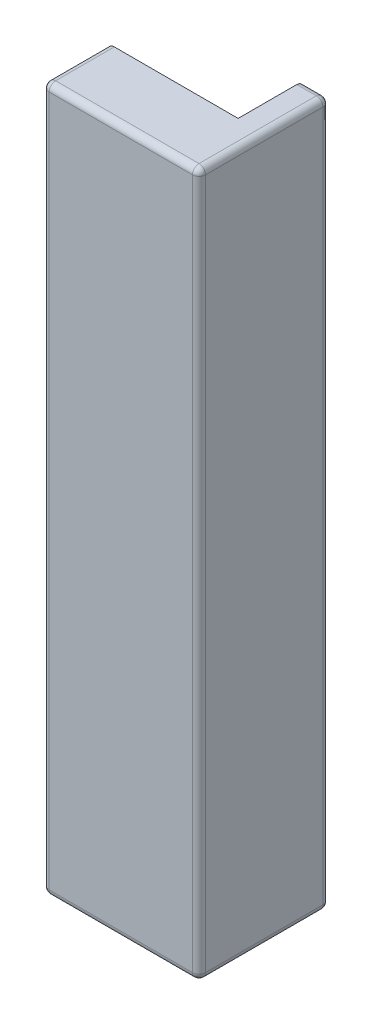
SolidWorks part; units mm, degrees
ref_plane "前基準面" through (0, 0, 0) normal (0, 0, 1) x (1, 0, 0)
ref_plane "上基準面" through (0, 0, 0) normal (0, 1, 0) x (1, 0, 0)
ref_plane "右基準面" through (0, 0, 0) normal (1, 0, 0) x (0, 0, -1)
sketch "草圖1" plane through (0, 0, 0) normal (0, 0, 1) x (1, 0, 0)
  line L1 (-30.8979, 20.8535) -> (-18.8979, 20.8535)
  line L2 (-30.8979, 20.8535) -> (-30.8979, -33.1465)
  line L3 (-30.8979, -33.1465) -> (-18.8979, -33.1465)
  line L4 (-18.8979, 20.8535) -> (-18.8979, -33.1465)
  dimension "D1" = 54
  dimension "D2" = 12
extrude "填料-伸長1" add sketch "草圖1" along normal blind 10 contours L2 L1 L4 L3
sketch "草圖2" plane through (-30.8979, 0, 0) normal (-1, 0, 0) x (0, 0, 1)
  line L0 (0, 20.8535) -> (0, -33.1465) construction
  line L1 (0, 18.8535) -> (8, 18.8535)
  line L2 (0, 18.8535) -> (0, -31.1465)
  line L3 (0, -31.1465) -> (8, -31.1465)
  line L4 (8, 18.8535) -> (8, -31.1465)
  line L5 (10, 20.8535) -> (0, 20.8535) construction
  dimension "D1" = 50
  dimension "D2" = 8
  dimension "D3" = 2
extrude "除料-伸長1" cut sketch "草圖2" against normal blind 10
sketch "草圖3" plane through (-30.8979, 0, 0) normal (-1, 0, 0) x (0, 0, 1)
  line L0 (10, 20.8535) -> (10, -33.1465) construction
  line L1 (5, 23.1696) -> (-8.5659, 23.1696)
  line L2 (5, 23.1696) -> (5, -34.6192)
  line L3 (5, -34.6192) -> (-8.5659, -34.6192)
  line L4 (-8.5659, 23.1696) -> (-8.5659, -34.6192)
  dimension "D1" = 5
extrude "除料-伸長2" cut sketch "草圖3" against normal blind 10
sketch "草圖4" plane through (-20.8979, 0, 0) normal (-1, 0, 0) x (0, 0, 1)
  line L5 (8, 18.8535) -> (5, 18.8535)
  line L6 (8, 18.8535) -> (8, -31.1465)
  line L7 (8, -31.1465) -> (5, -31.1465)
  line L8 (5, 18.8535) -> (5, -31.1465)
extrude "除料-伸長3" cut sketch "草圖4" against normal blind 1
fillet "圓角1" radius 0.5 19 edges at (-19.8979, 20.8535, 0) (-19.8979, -33.1465, 0) (-30.8979, -33.1465, 7.5) (-30.8979, 20.8535, 7.5) (-18.8979, -6.1465, 0) (-30.8979, -6.1465, 10) (-24.8979, 20.8535, 10) (-18.8979, 20.8535, 5) (-24.8979, -33.1465, 10) (-18.8979, -33.1465, 5) (-18.8979, -6.1465, 10) (-30.8979, -31.1465, 6.5) (-30.8979, -6.1465, 8) (-30.8979, 18.8535, 6.5) (-19.8979, -31.1465, 6.5) (-19.8979, 18.8535, 6.5) (-19.8979, -6.1465, 5) (-19.8979, -6.1465, 8) (-20.8979, -6.1465, 5)
